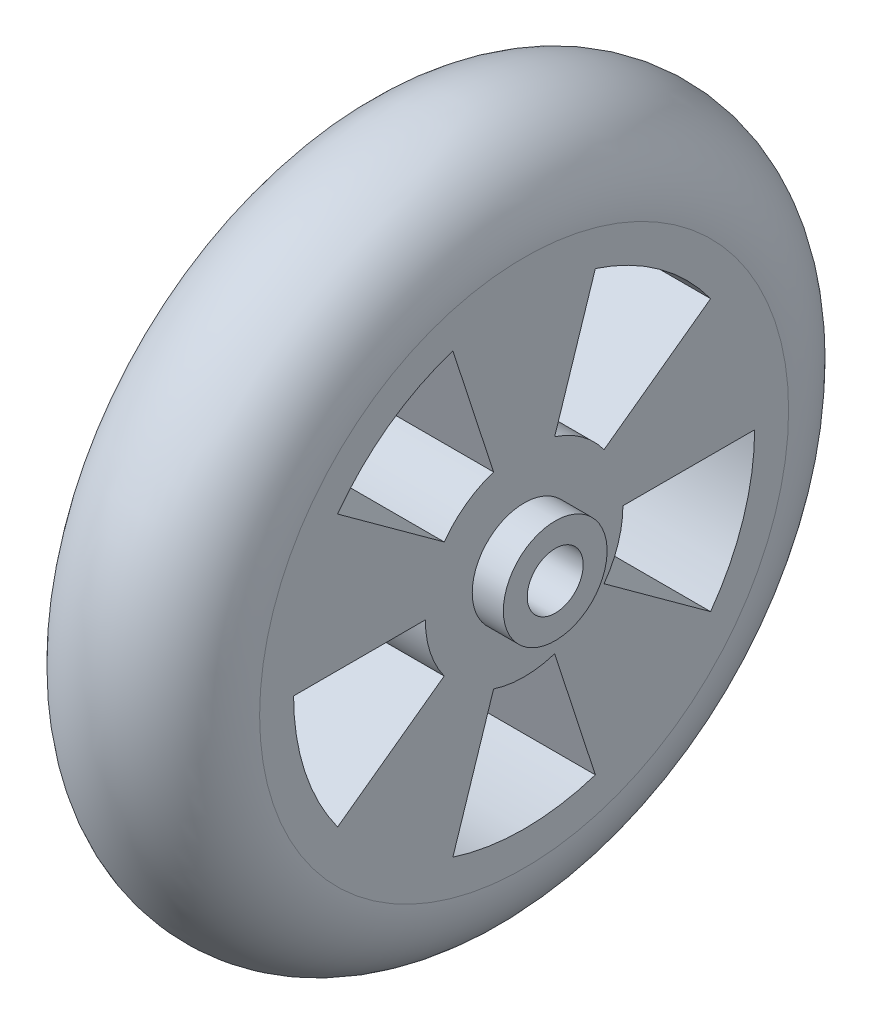
SolidWorks part; units mm, degrees
material "Rubber"
ref_plane "Front Plane" through (0, 0, 0) normal (0, 0, 1) x (1, 0, 0)
ref_plane "Top Plane" through (0, 0, 0) normal (0, 1, 0) x (1, 0, 0)
ref_plane "Right Plane" through (0, 0, 0) normal (1, 0, 0) x (0, 0, -1)
sketch "Sketch1" plane through (0, 0, 0) normal (0, 0, 1) x (1, 0, 0)
  line L0 (0, 25.5) -> (0, 0)
  line L1 (0, 0) -> (20, 0)
  line L2 (20, 0) -> (20, 5)
  line L3 (20, 5) -> (17, 5)
  line L4 (17, 5) -> (17, 25.5)
  line L5 (0, 25.5) -> (17, 25.5) construction
  arc A0 (0, 25.5) -> (17, 25.5) centre (8.5, 25.5) cw
  point P9 (8.5, 34)
  dimension "D1" = 34
  dimension "D2" = 17
  dimension "D3" = 3
  dimension "D4" = 5
revolve "Revolve1" add sketch "Sketch1" angle 360 about L1
sketch "Sketch2" plane through (0, 0, 0) normal (1, 0, 0) x (0, 0, -1)
  circle A0 centre (0, 0) radius 2.7
  dimension "D1" = 5.4
extrude "Cut-Extrude1" cut sketch "Sketch2" along normal through all
sketch "Sketch3" plane through (0, 0, 0) normal (1, 0, 0) x (0, 0, -1)
  line L0 (0, 0) -> (6.8679, 21.1372)
  line L1 (0, 0) -> (17.9804, 13.0635)
  line L2 (0, 0) -> (0, 34) construction
  line L3 (0, 0) -> (22.225, 0)
  line L4 (0, 0) -> (17.9804, -13.0635)
  line L5 (0, 0) -> (6.8679, -21.1372)
  line L6 (0, 0) -> (-6.8679, -21.1372)
  line L7 (0, 0) -> (-17.9804, -13.0635)
  line L8 (0, 0) -> (-22.225, 0)
  line L9 (0, 0) -> (-17.9804, 13.0635)
  line L10 (0, 0) -> (-6.8679, 21.1372)
  circle A0 centre (0, 0) radius 9.525 construction
  circle A1 centre (0, 0) radius 22.225 construction
  arc A2 (2.9434, 9.0588) -> (7.7059, 5.5987) centre (0, 0) cw
  arc A3 (6.8679, 21.1372) -> (17.9804, 13.0635) centre (0, 0) cw
  circle A4 centre (0, 0) radius 34 construction
  arc A5 (22.225, 0) -> (17.9804, -13.0635) centre (0, 0) cw
  arc A6 (9.525, 0) -> (7.7059, -5.5987) centre (0, 0) cw
  arc A7 (6.8679, -21.1372) -> (-6.8679, -21.1372) centre (0, 0) cw
  arc A8 (2.9434, -9.0588) -> (-2.9434, -9.0588) centre (0, 0) cw
  arc A9 (-17.9804, -13.0635) -> (-22.225, 0) centre (0, 0) cw
  arc A10 (-7.7059, -5.5987) -> (-9.525, 0) centre (0, 0) cw
  arc A11 (-17.9804, 13.0635) -> (-6.8679, 21.1372) centre (0, 0) cw
  arc A12 (-7.7059, 5.5987) -> (-2.9434, 9.0588) centre (0, 0) cw
  point P30 (0, 0)
  dimension "D1" = 19.05
  dimension "D2" = 44.45
  dimension "D3" = 18
  dimension "D4" = 36
  dimension "D5" = 5
extrude "Cut-Extrude2" cut sketch "Sketch3" along normal through all contours L9 A12 L10 A11 | A3 L0 A2 L1 | L3 A6 L4 A5 | L5 A8 L6 A7 | L7 A10 L8 A9 region at (0, 13.3067, -9.6679) region at (0, -5.0827, -15.6429) region at (0, -16.448, 0) region at (0, -5.0827, 15.6429) region at (0, 13.3067, 9.6679)
